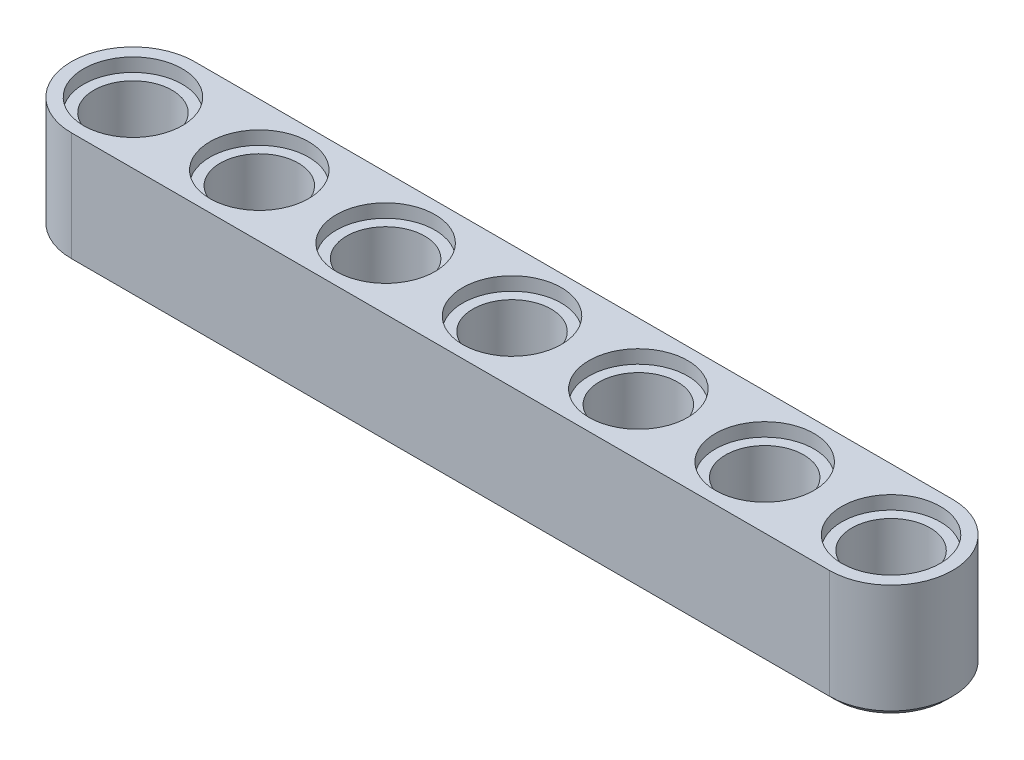
SolidWorks part; units mm, degrees
ref_plane "Front Plane" through (0, 0, 0) normal (0, 0, 1) x (1, 0, 0)
ref_plane "Top Plane" through (0, 0, 0) normal (0, 1, 0) x (1, 0, 0)
ref_plane "Right Plane" through (0, 0, 0) normal (1, 0, 0) x (0, 0, -1)
sketch "Sketch1" plane through (0, 0, 0) normal (0, 1, 0) x (1, 0, 0)
  line L0 (0, 0) -> (48, 0) construction
  line L1 (0, 3.9) -> (48, 3.9)
  line L2 (0, -3.9) -> (48, -3.9)
  arc A0 (0, 3.9) -> (0, -3.9) centre (0, 0) ccw
  arc A1 (48, -3.9) -> (48, 3.9) centre (48, 0) ccw
  point P3 (24, 0)
  dimension "D1" = 48
  dimension "D2" = 7.8
extrude "Boss-Extrude1" add sketch "Sketch1" along normal blind 7.3
sketch "Sketch2" plane through (0, 7.3, 0) normal (0, 1, 0) x (1, 0, 0)
  circle A0 centre (0, 0) radius 2.475
  dimension "D1" = 4.95
extrude "Cut-Extrude1" cut sketch "Sketch2" against normal through all
sketch "Sketch3" plane through (0, 7.3, 0) normal (0, 1, 0) x (1, 0, 0)
  circle A0 centre (0, 0) radius 3.125
  dimension "D1" = 6.25
extrude "Cut-Extrude2" cut sketch "Sketch3" against normal blind 0.85
ref_plane "Plane1" through (0, 3.65, 0) normal (0, 1, 0) x (1, 0, 0)
mirror "Mirror1" about plane through (0, 3.65, 0) normal (0, 1, 0) of "Cut-Extrude2"
pattern_linear "LPattern1" count 7 spacing 8 along (1, 0, 0) of "Cut-Extrude1", "Cut-Extrude2", "Mirror1"
chamfer "Chamfer1" distance 0.4 angle 45 11 edges at (24, 0, 3.9) (51.9, 0, 0) (24, 0, -3.9) (-3.9, 0, 0) (0, 0, 3.125) (8, 0, 3.125) (16, 0, 3.125) (24, 0, 3.125) (32, 0, 3.125) (40, 0, 3.125) (48, 0, 3.125)
equation "\"Pitch\"= 8"
equation "\"Beam_Height\"= 7.8"
equation "\"Beam_Width\"= 7.3"
equation "\"Pin_Hole_Dia\"= 4.95"
equation "\"CBore_Dia\"= 6.25"
equation "\"CBore_Depth\"= 0.85"
equation "\"D2@Sketch1\"=\"Beam_Height\""
equation "\"D1@Boss-Extrude1\"=\"Beam_Width\""
equation "\"D1@Sketch2\"=\"Pin_Hole_Dia\""
equation "\"D1@Sketch3\"=\"CBore_Dia\""
equation "\"D1@Cut-Extrude2\"=\"CBore_Depth\""
equation "\"D3@LPattern1\"=\"Pitch\""
